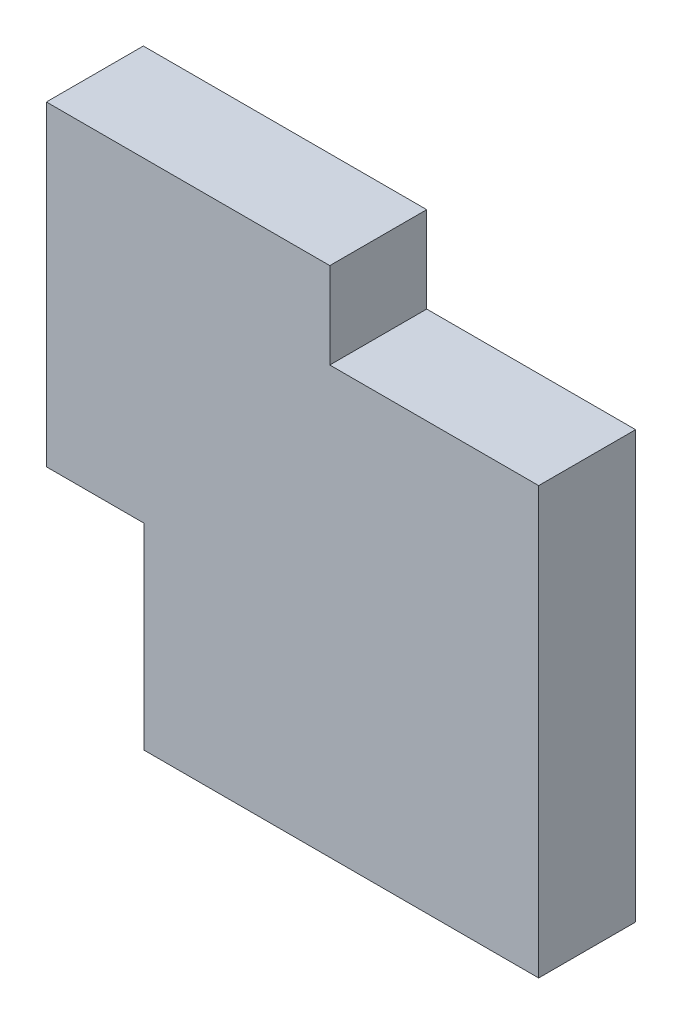
SolidWorks part; units mm, degrees
ref_plane "Front Plane" through (0, 0, 0) normal (0, 0, 1) x (1, 0, 0)
ref_plane "Top Plane" through (0, 0, 0) normal (0, 1, 0) x (1, 0, 0)
ref_plane "Right Plane" through (0, 0, 0) normal (1, 0, 0) x (0, 0, -1)
sketch "Sketch2" plane through (0, 0, 0) normal (0, 0, 1) x (1, 0, 0)
  line L0 (-65.1287, 67.6887) -> (-10.1287, 67.6887)
  line L1 (-6.6557, 48.5664) -> (44.6543, 48.5664)
  line L2 (-44.6543, -0.2836) -> (-44.6543, -48.5664)
  line L3 (-44.6543, -48.5664) -> (44.6543, -48.5664)
  line L4 (44.6543, 48.5664) -> (44.6543, -48.5664)
  line L5 (-44.6543, 48.5664) -> (44.6543, -48.5664) construction
  line L6 (-44.6543, -48.5664) -> (44.6543, 48.5664) construction
  line L7 (-68.6557, 69.7164) -> (-6.6557, 69.7164)
  line L8 (-68.6557, 69.7164) -> (-68.6557, -0.2836)
  line L9 (-68.6557, -0.2836) -> (-44.6543, -0.2836)
  line L10 (-6.6557, 69.7164) -> (-6.6557, 48.5664)
  line L15 (-10.1287, 64.6887) -> (-65.1287, 64.6887)
  circle A0 centre (-65.1287, 66.1887) radius 1.5
  circle A1 centre (-10.1287, 66.1887) radius 1.5
  circle A2 centre (0.6906, -4.2529) radius 1.5
  point P0 (0, 0)
  dimension "D1" = 55
  dimension "D2" = 113.31
  dimension "D3" = 2.0277
  dimension "D4" = 3.527
  dimension "D5" = 97.1328
  dimension "D6" = 62
  dimension "D7" = 21.15
  dimension "D8" = 89.3086
  dimension "D9" = 70
extrude "Boss-Extrude1" add sketch "Sketch2" along normal blind 20 and the other way blind 0.0001 contours L2 L3 L4 L1 L10 L7 L8 L9
sketch "Corner Hole" [suppressed] plane through (0, 0, 50.8) normal (0, 0, 1) x (1, 0, 0)
  line L0 (-44.6543, 48.5664) -> (-39.6585, 48.5664)
  line L1 (-39.6585, 48.5664) -> (-39.6585, 44.2603)
  line L2 (-39.6585, 44.2603) -> (-44.6543, 44.2603)
  line L3 (-44.6543, 48.5664) -> (-44.6543, 44.2603)
  line L4 (-44.4519, 45.394) -> (-44.4519, 44.9736)
  line L5 (-44.4519, 44.9736) -> (-44.1176, 44.9736)
  line L6 (-38.5629, 45.8871) -> (-38.3451, 45.8871)
  line L7 (-44.6543, 48.5664) -> (-44.0619, 48.5664)
  line L8 (-44.6543, 48.5664) -> (-44.6543, 47.9775)
  line L9 (-44.6543, 47.9775) -> (-44.0619, 47.9775)
  line L10 (-44.0619, 48.5664) -> (-44.0619, 47.9775)
  line L11 (-38.3451, 45.8871) -> (-38.3451, 46.034)
  line L12 (-38.3451, 46.034) -> (-38.5629, 46.034)
  line L13 (-38.5629, 46.034) -> (-38.5629, 46.2265)
  line L14 (-38.5629, 46.2265) -> (-38.3451, 46.2265)
  circle A0 centre (-42.441, 46.3496) radius 1.0726
  dimension "D1" = 2.2168
  dimension "D2" = 2.2132
  dimension "D3" = 0.2023
  dimension "D4" = 0.7132
shell "Shell3" thickness 3.81 removed face at (-18.8279, 17.3582, -0.0001) outward yes
sketch "Sketch9" plane through (0, 0, 20) normal (0, 0, -1) x (-1, 0, 0)
  line L0 (-44.6543, 48.5664) -> (-44.6543, -48.5664) construction
  line L1 (6.6557, 48.5664) -> (-44.6543, 48.5664) construction
  line L2 (-44.6543, 48.5664) -> (-38.3603, 48.5664)
  line L3 (-44.6543, 42.2724) -> (-44.6543, 48.5664)
  arc A0 (-44.6543, 42.2724) -> (-38.3603, 48.5664) centre (-44.6543, 48.5664) ccw
  circle A3 centre (-42.441, 46.3496) radius 1.0726
extrude "Boss-Extrude3" add sketch "Sketch9" along normal blind 3.0017
sketch "Sketch12" plane through (0, 0, 20) normal (0, 0, -1) x (-1, 0, 0)
  circle A0 centre (-42.4458, 46.3563) radius 1.0808
  circle A1 centre (41.5284, 46.9129) radius 0.0001
sketch "Sketch16" plane through (0, 0, 23.81) normal (0, 0, 1) x (1, 0, 0)
  line L0 (19.1455, 0) -> (-19.1455, 0) construction
  line L1 (40.3168, 48.0754) -> (44.1866, 48.0754)
  line L2 (40.3168, 48.0754) -> (40.3168, 44.621)
  line L3 (40.3168, 44.621) -> (44.1866, 44.621)
  line L4 (44.1866, 48.0754) -> (44.1866, 44.621)
  line L5 (0, -19.1455) -> (0, 19.1455) construction
  circle A0 centre (42.4458, 46.3563) radius 1.0808
  circle A1 centre (42.4458, -46.3563) radius 1.0808
  circle A2 centre (-42.4458, 46.3563) radius 1.0808
  circle A3 centre (-42.4458, -46.3563) radius 1.0808
mirror "Mirror1" about plane through (0, 0, 0) normal (0, 1, 0) of "Boss-Extrude3"
ref_axis "Axis2" through (48.4643, 52.3764, 23.81) along (-0.6778, -0.7347, -0.0277)
sketch "Sketch19" plane through (0, 0, 20) normal (0, 0, -1) x (-1, 0, 0)
  line L0 (44.6543, -48.5664) -> (-44.6543, -48.5664) construction
  line L1 (44.6543, -0.2836) -> (44.6543, -48.5664) construction
  line L2 (39.2995, -48.5664) -> (44.6543, -48.5664)
  line L3 (44.6543, -48.5664) -> (44.6543, -43.2116)
  arc A0 (39.2995, -48.5664) -> (44.6543, -43.2116) centre (44.6543, -48.5664) cw
  circle A1 centre (42.4458, -46.3563) radius 1.0808
extrude "Boss-Extrude4" add sketch "Sketch19" along normal blind 3 contours A1 | L3 A0 L2 region at (-42.4458, -46.3563, 20)
sketch "Sketch20" plane through (0, 0, 20) normal (0, 0, -1) x (-1, 0, 0)
  line L0 (68.6557, 69.7164) -> (68.6557, -0.2836) construction
  line L1 (68.6557, 69.7164) -> (6.6557, 69.7164) construction
  line L2 (68.6557, 69.7164) -> (68.6557, 63.7169)
  line L3 (68.6557, 69.7164) -> (62.6562, 69.7164)
  line L4 (68.6557, -0.2836) -> (44.6543, -0.2836) construction
  line L5 (68.6557, 5.7164) -> (68.6557, -0.2836)
  line L6 (68.6557, -0.2836) -> (62.6557, -0.2836)
  arc A0 (68.6557, 63.7169) -> (62.6562, 69.7164) centre (68.6557, 69.7164) cw
  arc A1 (68.6557, 5.7164) -> (62.6557, -0.2836) centre (68.6557, -0.2836) ccw
extrude "Boss-Extrude5" add sketch "Sketch20" along normal blind 17.32
sketch "Sketch22" plane through (0, 0, -0.0001) normal (0, 0, -1) x (-1, 0, 0)
  line L0 (2.8457, 73.5264) -> (72.4657, 73.5264)
  line L1 (72.4657, 73.5264) -> (72.4657, -4.0936)
  line L2 (72.4657, -4.0936) -> (48.4643, -4.0936)
  line L3 (48.4643, -4.0936) -> (48.4643, -52.3764)
  line L4 (48.4643, -52.3764) -> (-48.4643, -52.3764)
  line L5 (-48.4643, -52.3764) -> (-48.4643, 52.3764)
  line L6 (-48.4643, 52.3764) -> (2.8457, 52.3764)
  line L7 (2.8457, 52.3764) -> (2.8457, 73.5264)
  line L8 (6.6557, 69.7164) -> (68.6557, 69.7164)
  line L9 (68.6557, 69.7164) -> (68.6557, -0.2836)
  line L10 (68.6557, -0.2836) -> (44.6543, -0.2836)
  line L11 (44.6543, -0.2836) -> (44.6543, -48.5664)
  line L12 (44.6543, -48.5664) -> (-44.6543, -48.5664)
  line L13 (-44.6543, -48.5664) -> (-44.6543, 48.5664)
  line L14 (-44.6543, 48.5664) -> (6.6557, 48.5664)
  line L15 (6.6557, 48.5664) -> (6.6557, 69.7164)
  line L16 (6.6557, 69.7164) -> (6.6557, 48.5664) construction
  line L17 (6.6557, 48.5664) -> (6.6557, -48.5664) construction
  line L18 (44.6543, -0.2836) -> (6.6557, 0) construction
  line L24 (47.6, -1.3486) -> (45.7937, -1.3486)
  line L25 (47.6, -1.3486) -> (47.6, -3.3159)
  line L26 (47.6, -3.3159) -> (45.7937, -3.3159)
  line L27 (45.7937, -1.3486) -> (45.7937, -3.3159)
  line L28 (47.6, -1.3486) -> (45.7937, -3.3159) construction
  line L29 (47.6, -3.3159) -> (45.7937, -1.3486) construction
  line L33 (47.4429, -49.3782) -> (45.6366, -49.3782)
  line L34 (47.4429, -49.3782) -> (47.4429, -51.3455)
  line L35 (47.4429, -51.3455) -> (45.6366, -51.3455)
  line L36 (45.6366, -49.3782) -> (45.6366, -51.3455)
  line L37 (5.5605, 51.4472) -> (3.7542, 51.4472)
  line L38 (5.5605, 51.4472) -> (5.5605, 49.4799)
  line L39 (5.5605, 49.4799) -> (3.7542, 49.4799)
  line L40 (3.7542, 51.4472) -> (3.7542, 49.4799)
  line L41 (-45.6795, 51.2032) -> (-47.4858, 51.2032)
  line L42 (-45.6795, 51.2032) -> (-45.6795, 49.2359)
  line L43 (-45.6795, 49.2359) -> (-47.4858, 49.2359)
  line L44 (-47.4858, 51.2032) -> (-47.4858, 49.2359)
  line L45 (-45.4826, -49.2962) -> (-47.2889, -49.2962)
  line L46 (-45.4826, -49.2962) -> (-45.4826, -51.2635)
  line L47 (-45.4826, -51.2635) -> (-47.2889, -51.2635)
  line L48 (-47.2889, -49.2962) -> (-47.2889, -51.2635)
  line L50 (-47.4858, 51.2032) -> (-45.6795, 51.2032)
  line L51 (-47.4858, 51.2032) -> (-47.4858, 49.2359)
  line L52 (-47.4858, 49.2359) -> (-45.6795, 49.2359)
  line L53 (-45.6795, 51.2032) -> (-45.6795, 49.2359)
  line L54 (-47.4858, 51.2032) -> (-45.6795, 49.2359) construction
  line L55 (-47.4858, 49.2359) -> (-45.6795, 51.2032) construction
  point P60 (-46.5826, 50.2196)
extrude "Cut-Extrude1" cut sketch "Sketch22" against normal blind 5 contours L33 L36 L35 L34 | L24 L27 L26 L25 | L45 L48 L47 L46 | L41 L44 L43 L42 | L37 L40 L39 L38 region at (-46.6968, -2.3323, -0.0001) region at (-46.5397, -50.3618, -0.0001) region at (46.5826, 50.2196, -0.0001) region at (46.3857, -50.2799, -0.0001)
